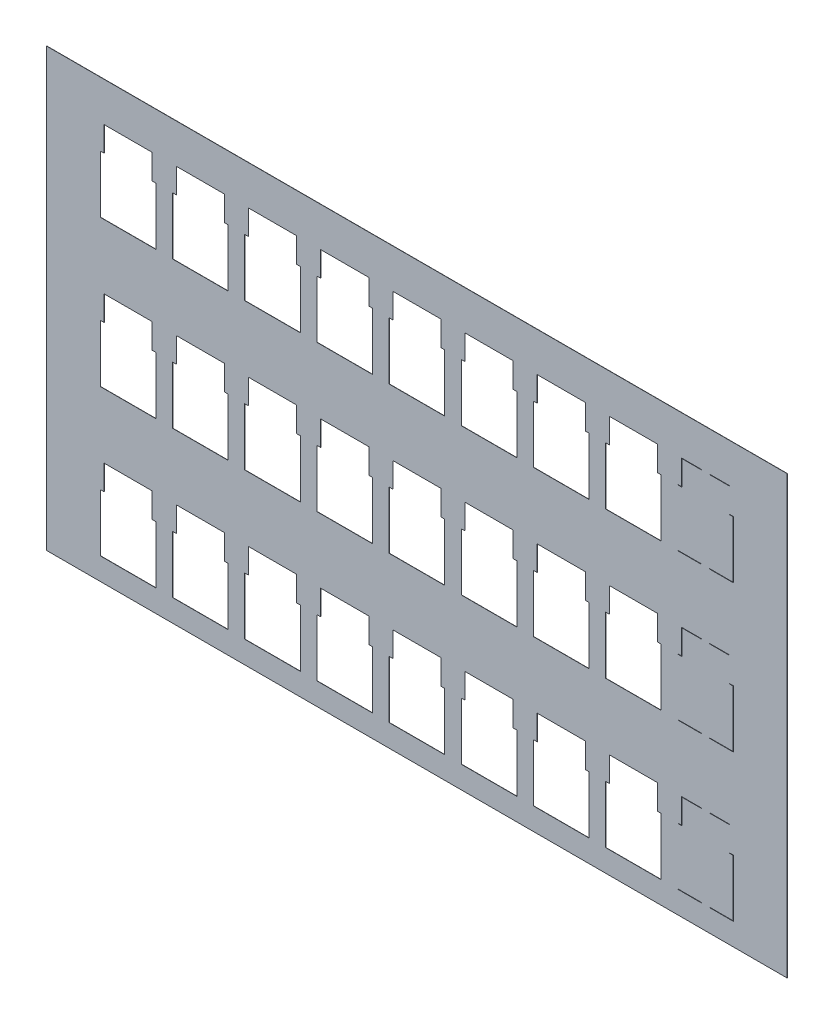
SolidWorks part; units mm, degrees
ref_plane "Front Plane" through (0, 0, 0) normal (0, 0, 1) x (1, 0, 0)
ref_plane "Top Plane" through (0, 0, 0) normal (0, 1, 0) x (1, 0, 0)
ref_plane "Right Plane" through (0, 0, 0) normal (1, 0, 0) x (0, 0, -1)
sketch "Model" plane through (0, 0, 0) normal (0, 0, 1) x (1, 0, 0)
  line L0 (1790, 852) -> (1640, 852)
  line L1 (1640, 852) -> (1640, 1007)
  line L2 (1640, 1007) -> (1650, 1007)
  line L3 (1650, 1007) -> (1650, 1074)
  line L4 (1650, 1074) -> (1780, 1074)
  line L5 (1780, 1074) -> (1780, 1007)
  line L6 (1780, 1007) -> (1790, 1007)
  line L7 (1790, 1007) -> (1790, 852)
  line L8 (1595, 852) -> (1445, 852)
  line L9 (1445, 852) -> (1445, 1007)
  line L10 (1445, 1007) -> (1455, 1007)
  line L11 (1455, 1007) -> (1455, 1074)
  line L12 (1455, 1074) -> (1585, 1074)
  line L13 (1585, 1074) -> (1585, 1007)
  line L14 (1585, 1007) -> (1595, 1007)
  line L15 (1595, 1007) -> (1595, 852)
  line L16 (1400, 852) -> (1250, 852)
  line L17 (1250, 852) -> (1250, 1007)
  line L18 (1250, 1007) -> (1260, 1007)
  line L19 (1260, 1007) -> (1260, 1074)
  line L20 (1260, 1074) -> (1390, 1074)
  line L21 (1390, 1074) -> (1390, 1007)
  line L22 (1390, 1007) -> (1400, 1007)
  line L23 (1400, 1007) -> (1400, 852)
  line L24 (1205, 852) -> (1055, 852)
  line L25 (1055, 852) -> (1055, 1007)
  line L26 (1055, 1007) -> (1065, 1007)
  line L27 (1065, 1007) -> (1065, 1074)
  line L28 (1065, 1074) -> (1195, 1074)
  line L29 (1195, 1074) -> (1195, 1007)
  line L30 (1195, 1007) -> (1205, 1007)
  line L31 (1205, 1007) -> (1205, 852)
  line L32 (1010, 852) -> (860, 852)
  line L33 (860, 852) -> (860, 1007)
  line L34 (860, 1007) -> (870, 1007)
  line L35 (870, 1007) -> (870, 1074)
  line L36 (870, 1074) -> (1000, 1074)
  line L37 (1000, 1074) -> (1000, 1007)
  line L38 (1000, 1007) -> (1010, 1007)
  line L39 (1010, 1007) -> (1010, 852)
  line L40 (815, 852) -> (665, 852)
  line L41 (665, 852) -> (665, 1007)
  line L42 (665, 1007) -> (675, 1007)
  line L43 (675, 1007) -> (675, 1074)
  line L44 (675, 1074) -> (805, 1074)
  line L45 (805, 1074) -> (805, 1007)
  line L46 (805, 1007) -> (815, 1007)
  line L47 (815, 1007) -> (815, 852)
  line L48 (620, 852) -> (470, 852)
  line L49 (470, 852) -> (470, 1007)
  line L50 (470, 1007) -> (480, 1007)
  line L51 (480, 1007) -> (480, 1074)
  line L52 (480, 1074) -> (610, 1074)
  line L53 (610, 1074) -> (610, 1007)
  line L54 (610, 1007) -> (620, 1007)
  line L55 (620, 1007) -> (620, 852)
  line L56 (425, 852) -> (275, 852)
  line L57 (275, 852) -> (275, 1007)
  line L58 (275, 1007) -> (285, 1007)
  line L59 (285, 1007) -> (285, 1074)
  line L60 (285, 1074) -> (415, 1074)
  line L61 (415, 1074) -> (415, 1007)
  line L62 (415, 1007) -> (425, 1007)
  line L63 (425, 1007) -> (425, 852)
  line L64 (230, 852) -> (80, 852)
  line L65 (80, 852) -> (80, 1007)
  line L66 (80, 1007) -> (90, 1007)
  line L67 (90, 1007) -> (90, 1074)
  line L68 (90, 1074) -> (220, 1074)
  line L69 (220, 1074) -> (220, 1007)
  line L70 (220, 1007) -> (230, 1007)
  line L71 (230, 1007) -> (230, 852)
  line L72 (1790, 456) -> (1640, 456)
  line L73 (1640, 456) -> (1640, 611)
  line L74 (1640, 611) -> (1650, 611)
  line L75 (1650, 611) -> (1650, 678)
  line L76 (1650, 678) -> (1780, 678)
  line L77 (1780, 678) -> (1780, 611)
  line L78 (1780, 611) -> (1790, 611)
  line L79 (1790, 611) -> (1790, 456)
  line L80 (1595, 456) -> (1445, 456)
  line L81 (1445, 456) -> (1445, 611)
  line L82 (1445, 611) -> (1455, 611)
  line L83 (1455, 611) -> (1455, 678)
  line L84 (1455, 678) -> (1585, 678)
  line L85 (1585, 678) -> (1585, 611)
  line L86 (1585, 611) -> (1595, 611)
  line L87 (1595, 611) -> (1595, 456)
  line L88 (1400, 456) -> (1250, 456)
  line L89 (1250, 456) -> (1250, 611)
  line L90 (1250, 611) -> (1260, 611)
  line L91 (1260, 611) -> (1260, 678)
  line L92 (1260, 678) -> (1390, 678)
  line L93 (1390, 678) -> (1390, 611)
  line L94 (1390, 611) -> (1400, 611)
  line L95 (1400, 611) -> (1400, 456)
  line L96 (1205, 456) -> (1055, 456)
  line L97 (1055, 456) -> (1055, 611)
  line L98 (1055, 611) -> (1065, 611)
  line L99 (1065, 611) -> (1065, 678)
  line L100 (1065, 678) -> (1195, 678)
  line L101 (1195, 678) -> (1195, 611)
  line L102 (1195, 611) -> (1205, 611)
  line L103 (1205, 611) -> (1205, 456)
  line L104 (1010, 456) -> (860, 456)
  line L105 (860, 456) -> (860, 611)
  line L106 (860, 611) -> (870, 611)
  line L107 (870, 611) -> (870, 678)
  line L108 (870, 678) -> (1000, 678)
  line L109 (1000, 678) -> (1000, 611)
  line L110 (1000, 611) -> (1010, 611)
  line L111 (1010, 611) -> (1010, 456)
  line L112 (815, 456) -> (665, 456)
  line L113 (665, 456) -> (665, 611)
  line L114 (665, 611) -> (675, 611)
  line L115 (675, 611) -> (675, 678)
  line L116 (675, 678) -> (805, 678)
  line L117 (805, 678) -> (805, 611)
  line L118 (805, 611) -> (815, 611)
  line L119 (815, 611) -> (815, 456)
  line L120 (620, 456) -> (470, 456)
  line L121 (470, 456) -> (470, 611)
  line L122 (470, 611) -> (480, 611)
  line L123 (480, 611) -> (480, 678)
  line L124 (480, 678) -> (610, 678)
  line L125 (610, 678) -> (610, 611)
  line L126 (610, 611) -> (620, 611)
  line L127 (620, 611) -> (620, 456)
  line L128 (425, 456) -> (275, 456)
  line L129 (275, 456) -> (275, 611)
  line L130 (275, 611) -> (285, 611)
  line L131 (285, 611) -> (285, 678)
  line L132 (285, 678) -> (415, 678)
  line L133 (415, 678) -> (415, 611)
  line L134 (415, 611) -> (425, 611)
  line L135 (425, 611) -> (425, 456)
  line L136 (230, 456) -> (80, 456)
  line L137 (80, 456) -> (80, 611)
  line L138 (80, 611) -> (90, 611)
  line L139 (90, 611) -> (90, 678)
  line L140 (90, 678) -> (220, 678)
  line L141 (220, 678) -> (220, 611)
  line L142 (220, 611) -> (230, 611)
  line L143 (230, 611) -> (230, 456)
  line L144 (1790, 60) -> (1640, 60)
  line L145 (1640, 60) -> (1640, 215)
  line L146 (1640, 215) -> (1650, 215)
  line L147 (1650, 215) -> (1650, 282)
  line L148 (1650, 282) -> (1780, 282)
  line L149 (1780, 282) -> (1780, 215)
  line L150 (1780, 215) -> (1790, 215)
  line L151 (1790, 215) -> (1790, 60)
  line L152 (1595, 60) -> (1445, 60)
  line L153 (1445, 60) -> (1445, 215)
  line L154 (1445, 215) -> (1455, 215)
  line L155 (1455, 215) -> (1455, 282)
  line L156 (1455, 282) -> (1585, 282)
  line L157 (1585, 282) -> (1585, 215)
  line L158 (1585, 215) -> (1595, 215)
  line L159 (1595, 215) -> (1595, 60)
  line L160 (1400, 60) -> (1250, 60)
  line L161 (1250, 60) -> (1250, 215)
  line L162 (1250, 215) -> (1260, 215)
  line L163 (1260, 215) -> (1260, 282)
  line L164 (1260, 282) -> (1390, 282)
  line L165 (1390, 282) -> (1390, 215)
  line L166 (1390, 215) -> (1400, 215)
  line L167 (1400, 215) -> (1400, 60)
  line L168 (1205, 60) -> (1055, 60)
  line L169 (1055, 60) -> (1055, 215)
  line L170 (1055, 215) -> (1065, 215)
  line L171 (1065, 215) -> (1065, 282)
  line L172 (1065, 282) -> (1195, 282)
  line L173 (1195, 282) -> (1195, 215)
  line L174 (1195, 215) -> (1205, 215)
  line L175 (1205, 215) -> (1205, 60)
  line L176 (1010, 60) -> (860, 60)
  line L177 (860, 60) -> (860, 215)
  line L178 (860, 215) -> (870, 215)
  line L179 (870, 215) -> (870, 282)
  line L180 (870, 282) -> (1000, 282)
  line L181 (1000, 282) -> (1000, 215)
  line L182 (1000, 215) -> (1010, 215)
  line L183 (1010, 215) -> (1010, 60)
  line L184 (815, 60) -> (665, 60)
  line L185 (665, 60) -> (665, 215)
  line L186 (665, 215) -> (675, 215)
  line L187 (675, 215) -> (675, 282)
  line L188 (675, 282) -> (805, 282)
  line L189 (805, 282) -> (805, 215)
  line L190 (805, 215) -> (815, 215)
  line L191 (815, 215) -> (815, 60)
  line L192 (620, 60) -> (470, 60)
  line L193 (470, 60) -> (470, 215)
  line L194 (470, 215) -> (480, 215)
  line L195 (480, 215) -> (480, 282)
  line L196 (480, 282) -> (610, 282)
  line L197 (610, 282) -> (610, 215)
  line L198 (610, 215) -> (620, 215)
  line L199 (620, 215) -> (620, 60)
  line L200 (425, 60) -> (275, 60)
  line L201 (275, 60) -> (275, 215)
  line L202 (275, 215) -> (285, 215)
  line L203 (285, 215) -> (285, 282)
  line L204 (285, 282) -> (415, 282)
  line L205 (415, 282) -> (415, 215)
  line L206 (415, 215) -> (425, 215)
  line L207 (425, 215) -> (425, 60)
  line L208 (230, 60) -> (80, 60)
  line L209 (80, 60) -> (80, 215)
  line L210 (80, 215) -> (90, 215)
  line L211 (90, 215) -> (90, 282)
  line L212 (90, 282) -> (220, 282)
  line L213 (220, 282) -> (220, 215)
  line L214 (220, 215) -> (230, 215)
  line L215 (230, 215) -> (230, 60)
  line L216 (0, 1180) -> (0, 0)
  line L217 (0, 0) -> (1870, 0)
  line L218 (1870, 0) -> (1870, 1180)
  line L219 (1870, 1180) -> (0, 1180)
base flange "Base-Flange1" sketch "Model" thickness 0.6 reverse thickness direction no parameters "D1"=0.7366
sketch "Sketch1" plane through (0, 0, 0) normal (0, 0, 1) x (1, 0, 0)
  line L16 (1651, 1006) -> (1651, 1073)
  line L17 (1651, 1073) -> (1704, 1073)
  line L18 (1779, 1073) -> (1779, 1006)
  line L19 (1779, 1006) -> (1789, 1006)
  line L20 (1789, 1006) -> (1789, 853)
  line L21 (1789, 853) -> (1726, 853)
  line L22 (1641, 853) -> (1641, 1006)
  line L23 (1641, 1006) -> (1651, 1006)
  line L24 (1704, 1074) -> (1726, 1074)
  line L25 (1651, 610) -> (1651, 677)
  line L26 (1726, 1073) -> (1726, 1074)
  line L27 (1704, 1073) -> (1704, 1074)
  line L28 (1704, 852) -> (1726, 852)
  line L29 (1651, 677) -> (1704, 677)
  line L30 (1704, 853) -> (1704, 852)
  line L31 (1726, 853) -> (1726, 852)
  line L32 (1704, 853) -> (1641, 853)
  line L33 (1726, 1073) -> (1779, 1073)
  line L34 (1779, 677) -> (1779, 610)
  line L35 (1779, 610) -> (1789, 610)
  line L36 (1789, 610) -> (1789, 457)
  line L37 (1789, 457) -> (1726, 457)
  line L38 (1641, 457) -> (1641, 610)
  line L39 (1641, 610) -> (1651, 610)
  line L40 (1704, 678) -> (1726, 678)
  line L41 (1726, 677) -> (1726, 678)
  line L42 (1704, 677) -> (1704, 678)
  line L43 (1704, 456) -> (1726, 456)
  line L44 (1704, 457) -> (1704, 456)
  line L45 (1726, 457) -> (1726, 456)
  line L46 (1704, 457) -> (1641, 457)
  line L47 (1726, 677) -> (1779, 677)
  line L48 (1651, 214) -> (1651, 281)
  line L49 (1651, 281) -> (1704, 281)
  line L50 (1779, 281) -> (1779, 214)
  line L51 (1779, 214) -> (1789, 214)
  line L52 (1789, 214) -> (1789, 61)
  line L53 (1789, 61) -> (1726, 61)
  line L54 (1641, 61) -> (1641, 214)
  line L55 (1641, 214) -> (1651, 214)
  line L56 (1704, 282) -> (1726, 282)
  line L57 (1726, 281) -> (1726, 282)
  line L58 (1704, 281) -> (1704, 282)
  line L59 (1704, 60) -> (1726, 60)
  line L60 (1704, 61) -> (1704, 60)
  line L61 (1726, 61) -> (1726, 60)
  line L62 (1704, 61) -> (1641, 61)
  line L63 (1726, 281) -> (1779, 281)
  dimension "D1" = 3
base flange "Tab1" sketch "Sketch1" thickness 0.6 reverse thickness direction no parameters "D1"=0.7366
sketch "Sketch4" plane through (0, 0, 0) normal (0, 0, 1) x (1, 0, 0)
  line L1 (1870, 1180) -> (1935, 1180)
  line L2 (1870, 1180) -> (1870, 0)
  line L3 (1870, 0) -> (1935, 0)
  line L4 (1935, 1180) -> (1935, 0)
  line L5 (0, 1180) -> (-65, 1180)
  line L6 (0, 1180) -> (0, 0)
  line L7 (0, 0) -> (-65, 0)
  line L8 (-65, 1180) -> (-65, 0)
  dimension "D1" = 65
  dimension "D2" = 65
base flange "Tab2" sketch "Sketch4" thickness 0.6 reverse thickness direction no parameters "D1"=0.7366
sketch "Bend-Lines1" [suppressed] plane through (0, 0, 0) normal (0, 1, 0) x (1, 0, 0)
sketch "Bounding-Box1" [suppressed] plane through (0, 0, 0) normal (0, 1, 0) x (1, 0, 0)
sheet metal parameters "Sheet-Metal1" thickness 0.6 parameters "D1"=0.7366
flat pattern "Flat-Pattern1" [suppressed]
sketch "Bend-Lines2" plane through (0, 0, 0) normal (0, 1, 0) x (1, 0, 0)
sketch3d "Bounding-Box2" [suppressed]
  line L0 (0, 0, 0) -> (-1870, 0, 0) construction
  line L1 (0, 1180, 0) -> (-1870, 1180, 0) construction
  line L2 (0, 0, 0) -> (0, 1180, 0) construction
  line L3 (-1870, 0, 0) -> (-1870, 1180, 0) construction
sheet metal parameters "Sheet-Metal2" thickness 0.6 parameters "D1"=0.7366
flat pattern "Flat-Pattern2"
sketch "Bend-Lines3" plane through (0, 0, 0) normal (0, 1, 0) x (1, 0, 0)
sketch3d "Bounding-Box3" [suppressed]
  line L0 (0, 0, 0) -> (1870, 0, 0) construction
  line L1 (0, 1180, 0) -> (1870, 1180, 0) construction
  line L2 (0, 0, 0) -> (0, 1180, 0) construction
  line L3 (1870, 0, 0) -> (1870, 1180, 0) construction
sheet metal parameters "Sheet-Metal3" thickness 0.6 parameters "D1"=0.7366
flat pattern "Flat-Pattern3"
sketch "Bend-Lines4" plane through (0, 0, 0) normal (0, 1, 0) x (1, 0, 0)
sketch3d "Bounding-Box4" [suppressed]
  line L0 (-65, 0, 0) -> (1935, 0, 0) construction
  line L1 (-65, 1180, 0) -> (1935, 1180, 0) construction
  line L2 (-65, 0, 0) -> (-65, 1180, 0) construction
  line L3 (1935, 0, 0) -> (1935, 1180, 0) construction
